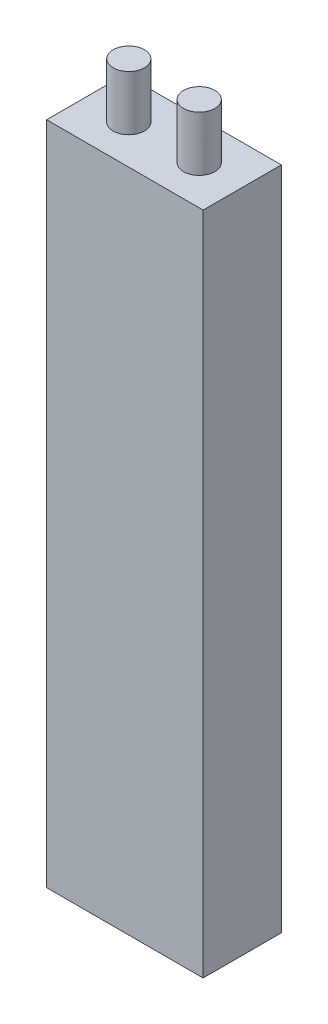
SolidWorks part; units mm, degrees
ref_plane "Front Plane" through (0, 0, 0) normal (0, 0, 1) x (1, 0, 0)
ref_plane "Top Plane" through (0, 0, 0) normal (0, 1, 0) x (1, 0, 0)
ref_plane "Right Plane" through (0, 0, 0) normal (1, 0, 0) x (0, 0, -1)
sketch "Sketch1" plane through (0, 0, 0) normal (0, 1, 0) x (1, 0, 0)
  line L1 (0, -10.671) -> (-21.342, -10.671) construction
  line L7 (-21.342, -10.671) -> (29.458, -10.671)
  line L8 (-21.342, -10.671) -> (-21.342, 14.729)
  line L9 (-21.342, 14.729) -> (29.458, 14.729)
  line L10 (29.458, -10.671) -> (29.458, 14.729)
extrude "Boss-Extrude1" add sketch "Sketch1" along normal blind 215.9 contours L9 L10 L7 L8
sketch "Sketch2" plane through (0, 215.9, 0) normal (0, 1, 0) x (1, 0, 0)
  line L0 (4.058, 14.729) -> (4.058, -10.671) construction
  line L1 (-21.342, 14.729) -> (29.458, 14.729) construction
  line L2 (-21.342, -10.671) -> (29.458, -10.671) construction
  line L3 (4.058, 2.029) -> (15.488, 2.029) construction
  line L4 (4.058, 2.029) -> (-7.372, 2.029) construction
  circle A0 centre (15.488, 2.029) radius 5.08
  circle A1 centre (-7.372, 2.029) radius 5.08
  dimension "D1" = 10.16
  dimension "D2" = 10.16
extrude "Boss-Extrude2" add sketch "Sketch2" along normal blind 17.78
